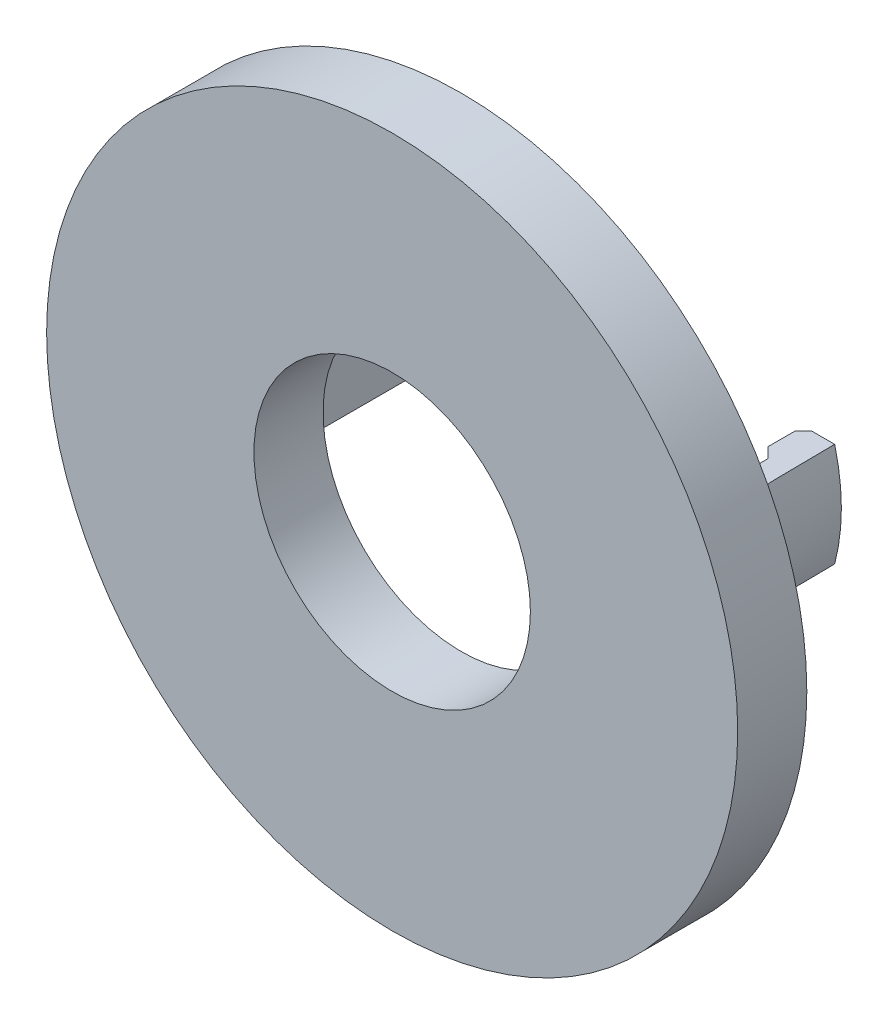
SolidWorks part; units mm, degrees
ref_plane "Front" through (0, 0, 0) normal (0, 0, 1) x (1, 0, 0)
ref_plane "Top" through (0, 0, 0) normal (0, 1, 0) x (1, 0, 0)
ref_plane "Right" through (0, 0, 0) normal (1, 0, 0) x (0, 0, -1)
sketch "Sketch1" plane through (0, 0, 0) normal (0, 0, 1) x (1, 0, 0)
  circle A0 centre (0, 0) radius 15.5
  circle A1 centre (0, 0) radius 25
  circle A2 centre (-2, 0) radius 15.5
  dimension "D1" = 31
  dimension "D2" = 50
  dimension "D3" = 2
sketch "Sketch4" plane through (0, 0, 0) normal (0, 0, 1) x (1, 0, 0)
  circle A0 centre (0, 0) radius 25
  dimension "D1" = 50
extrude "Boss-Extrude2" add sketch "Sketch4" along normal blind 5
sketch "Sketch5" plane through (0, 0, 5) normal (0, 0, 1) x (1, 0, 0)
  circle A0 centre (0, 0) radius 10
  dimension "D1" = 20
extrude "Cut-Extrude1" cut sketch "Sketch5" against normal through all
sketch "Sketch6" plane through (0, 0, 0) normal (0, 1, 0) x (1, 0, 0)
  line L0 (10, 0) -> (15.5, 0) construction
  line L1 (15.5, 0) -> (15.5, 13)
  line L2 (12.5, 2.5) -> (12.5, 9) construction
  line L3 (15.5, 13) -> (12.5, 13) construction
  line L4 (12.5, 13) -> (11.5, 12) construction
  line L5 (11.5, 10) -> (12.5, 9) construction
  line L6 (14.75, 7.0619) -> (14.75, 18.4381) construction
  line L7 (12.75, 9.4571) -> (12.75, 2.3964)
  line L8 (12.5, 2.5) -> (10, 0) construction
  line L9 (12.75, 9.4571) -> (12, 10.2071)
  line L10 (11.5, 12) -> (11.5, 10) construction
  line L11 (12, 10.2071) -> (12, 12.1464)
  line L12 (15.5, 0) -> (15.5, 12.75) construction
  line L13 (15.5, 0) -> (10.3536, 0)
  line L14 (12.75, 2.3964) -> (10.3536, 0)
  line L15 (12, 12.1464) -> (12.6036, 12.75)
  line L16 (12.6036, 12.75) -> (15.5, 12.75)
  spline S0 degree 2 poles (14.75, 12.75) (14.75, 3.4464) (15.5, 0) knots 0 0 0 1 1 1
  dimension "D2" = 1
  dimension "D3" = 4
  dimension "D4" = 13
  dimension "D5" = 4
  dimension "D6" = 0.25
  dimension "D7" = 0.25
  dimension "D8" = 0.25
  dimension "D9" = 0.5
  dimension "D10" = 225
  dimension "D11" = 5.5
  dimension "D12" = 0.25
  dimension "D13" = 135
  dimension "D14" = 0.5
  dimension "D15" = 0.75
extrude "Boss-Extrude3" add sketch "Sketch6" along normal blind 3.75 and the other way blind 3.75 contours L16 L15 L11 L9 L7 L14 | L12 L16 region at (15.1845, 0, -7.6129) region at (13.6006, 0, -5.9123)
extrude "Cut-Extrude2" cut sketch "Sketch1" against normal through all contours A1 A2 A0 region at (-24.2929, 0, 0)
ref_axis "Axis1" through (0, 0, 0) along (0, 0, -1)
revolve "Cut-Revolve1" cut sketch "Sketch6<4>" angle 360 about axis through (0, 0, 0) along (0, 0, -1) region at (15.1845, 0, -7.6129)
sketch "Sketch6<4>" plane through (0, 0, 0) normal (0, 1, 0) x (1, 0, 0) same geometry as "Sketch6"
mirror "Mirror1" about plane through (0, 0, 0) normal (1, 0, 0) of "Boss-Extrude3", "Cut-Extrude2", "Cut-Revolve1"
equation "\"mate_room\"= 0.25"
equation "\"D6@Sketch6\"=\"mate_room\""
equation "\"D8@Sketch6\"=\"mate_room\""
equation "\"D7@Sketch6\"=\"mate_room\""
equation "\"D9@Sketch6\"=\"removal_room\""
equation "\"D12@Sketch6\"=\"mate_room\""
equation "\"D14@Sketch6\"=\"removal_room\""
equation "\"removal_room\"= 0.5"
equation "\"large_inner_axle_diameter\"=20"
equation "\"D1@Sketch5\"=\"large_inner_axle_diameter\""
